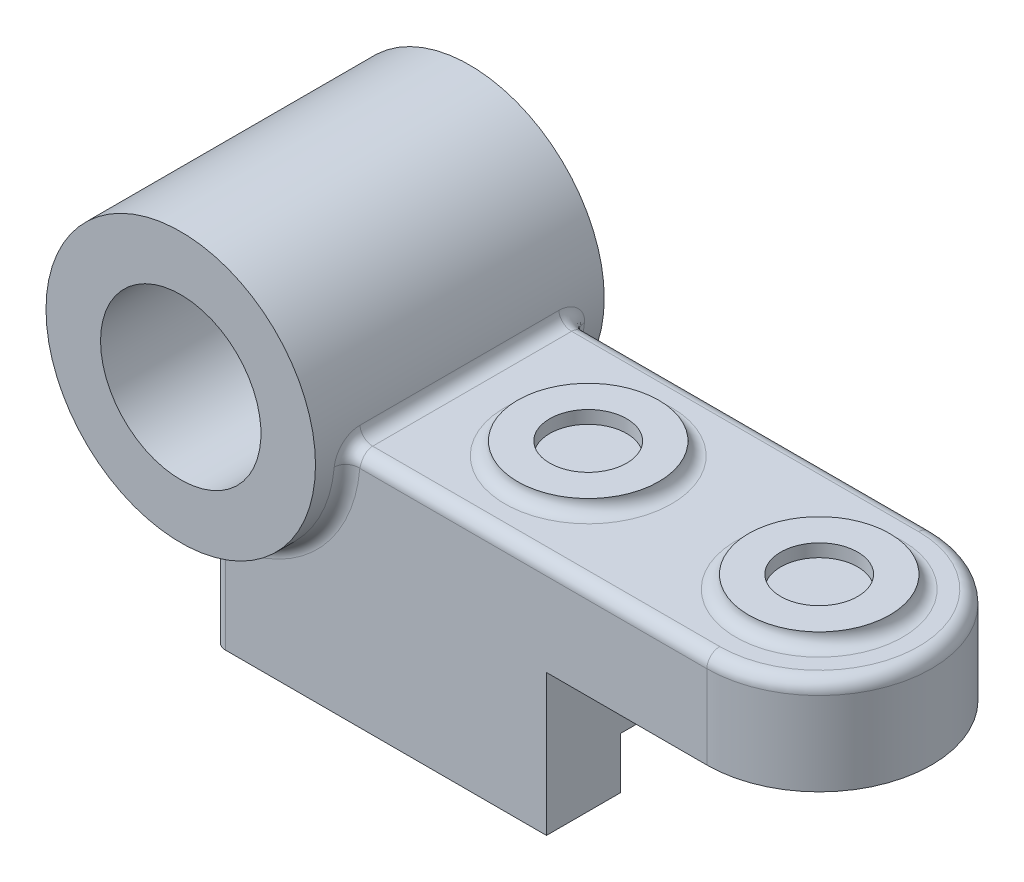
SolidWorks part; units mm, degrees
ref_plane "Front Plane" through (0, 0, 0) normal (0, 0, 1) x (1, 0, 0)
ref_plane "Top Plane" through (0, 0, 0) normal (0, 1, 0) x (1, 0, 0)
ref_plane "Right Plane" through (0, 0, 0) normal (1, 0, 0) x (0, 0, -1)
sketch "Sketch3" plane through (0, 0, 0) normal (0, 0, 1) x (1, 0, 0)
  line L0 (0, -21) -> (0, -37)
  line L1 (0, -37) -> (52, -37)
  line L2 (52, -37) -> (52, -15)
  line L3 (52, -15) -> (111.2558, -15)
  line L4 (111.2558, -15) -> (111.2558, 0)
  line L5 (111.2558, 0) -> (21, 0)
  circle A0 centre (0, 0) radius 21
  circle A1 centre (0, 0) radius 12.5
  dimension "D3" = 25
  dimension "D4" = 42
  dimension "D1" = 52
  dimension "D2" = 15
  dimension "D5" = 37
extrude "Boss-Extrude1" add sketch "Sketch3" along normal mid plane 45 contours A0 A1 region at (-14.4292, 14.4292, 0)
extrude "Boss-Extrude2" add sketch "Sketch3<3>" along normal mid plane 35 contours A0 L0 L1 L2 L3 L4 L5 region at (48.446, -15.8823, 0)
sketch "Sketch3<3>" plane through (0, 0, 0) normal (0, 0, 1) x (1, 0, 0) same geometry as "Sketch3"
sketch "Sketch5" plane through (52, 0, 0) normal (1, 0, 0) x (0, 0, -1)
  line L0 (6, -37) -> (6, -29)
  line L1 (-17.5, -37) -> (17.5, -37) construction
  line L2 (6, -29) -> (-6, -29)
  line L3 (-6, -29) -> (-6, -37)
  line L4 (0, 3.1403) -> (0, -2.7433) construction
  dimension "D1" = 8
  dimension "D2" = 12
extrude "Cut-Extrude1" cut sketch "Sketch5" against normal blind 53 and the other way through all
sketch "Sketch4" plane through (0, 0, 0) normal (0, 1, 0) x (1, 0, 0)
  line L0 (0, 0) -> (94.5, 0) construction
  line L1 (52, 6) -> (0, 6) construction
  line L2 (52, -6) -> (0, -6) construction
  line L3 (111.2558, -17.5) -> (21, -17.5) construction
  line L4 (111.2558, 17.5) -> (21, 17.5) construction
  circle A0 centre (41, 0) radius 11
  circle A1 centre (41, 0) radius 6
  circle A2 centre (77, 0) radius 11
  circle A3 centre (77, 0) radius 6
  circle A4 centre (77, 0) radius 17.5
  point P10 (94.5, 0)
  line M7 (111.2558, 17.5) -> (21, 17.5)
  line M9 (21, -17.5) -> (111.2558, -17.5)
  line M10 (111.2558, -17.5) -> (111.2558, 17.5)
  dimension "D3" = 22
  dimension "D4" = 22
  dimension "D1" = 36
  dimension "D2" = 77
extrude "Boss-Extrude3" add sketch "Sketch4" along normal blind 2 contours L0 A0 A1 | A0 L0 A1 | A2 L0 A3 | L0 A2 A3 region at (41, 0, -6.246) region at (49.5, 0, 0.246) region at (77, 0, -10.754) region at (68.5, 0, 0.246)
extrude "Cut-Extrude2" cut sketch "Sketch4<3>" against normal up to next contours A4 M9 M10 M7 region at (100.6282, 0, 0)
sketch "Sketch4<3>" plane through (0, 0, 0) normal (0, 1, 0) x (1, 0, 0) same geometry as "Sketch4"
fillet "Fillet1" radius 2 11 edges at (0, -21, 0) (14.8492, -14.8492, -17.5) (14.8492, -14.8492, 17.5) (49, 0, -17.5) (94.5, 0, 0) (49, 0, 17.5) (21, 0, 0) (0, -29, 17.5) (0, -29, -17.5) (41, 0, -11) (77, 0, -11)
